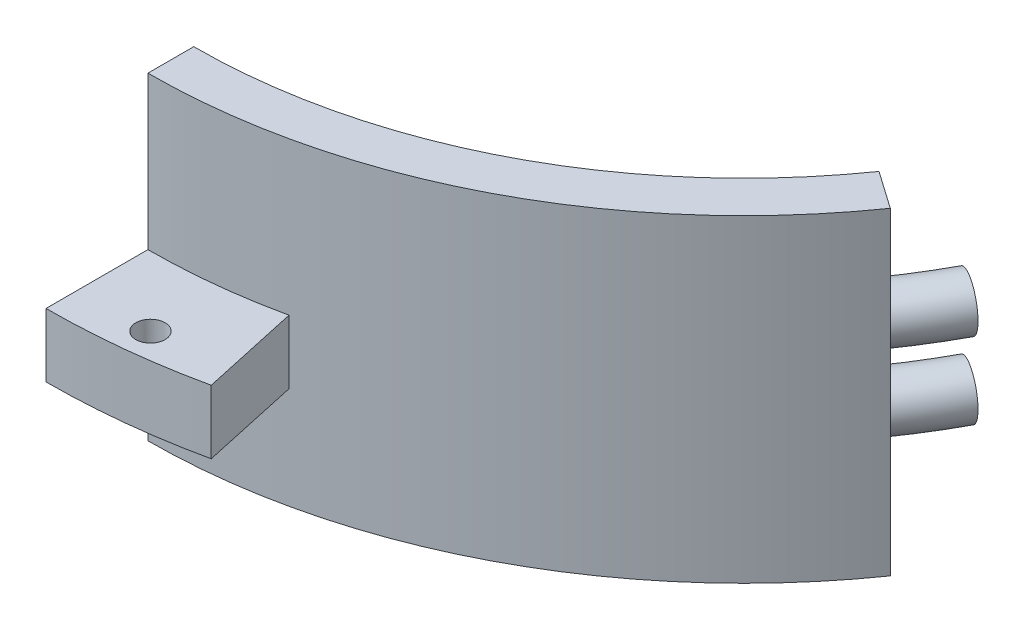
SolidWorks part; units mm, degrees
ref_plane "Front Plane" through (0, 0, 0) normal (0, 0, 1) x (1, 0, 0)
ref_plane "Top Plane" through (0, 0, 0) normal (0, 1, 0) x (1, 0, 0)
ref_plane "Right Plane" through (0, 0, 0) normal (1, 0, 0) x (0, 0, -1)
sketch "Sketch2" plane through (0, 0, 0) normal (0, 1, 0) x (1, 0, 0)
  line L0 (0, -46.8) -> (0, -43.2)
  line L1 (38.3363, -26.8434) -> (35.3874, -24.7785)
  line L2 (0, 0) -> (35.3874, -24.7785) construction
  circle A0 centre (0, 0) radius 46.8
  circle A1 centre (0, 0) radius 43.2
  dimension "D1" = 93.6
  dimension "D3" = 55
  dimension "D2" = 3.6
extrude "Boss-Extrude1" add sketch "Sketch2" along normal blind 25 contours A1 L0 A0 L1 region at (20.0007, 0, 38.421)
sketch "Sketch3" plane through (0, 25, 0) normal (0, 1, 0) x (1, 0, 0)
  line L0 (0, -43.2) -> (0, -40)
  line L1 (35.3874, -24.7785) -> (32.7661, -22.9431)
  line L2 (38.3363, -26.8434) -> (35.3874, -24.7785) construction
  circle A0 centre (0, 0) radius 40
  circle A2 centre (0, 0) radius 44.8
  arc M6 (35.3874, -24.7785) -> (0, -43.2) centre (0, 0) cw
  dimension "D1" = 80
  dimension "D2" = 89.6
extrude "Boss-Extrude2" add sketch "Sketch3" against normal blind 13 from offset 6 contours A0 L0 L1 M6 region at (18.4888, 25, 35.5166) offset against normal yes
sketch "Sketch4" plane through (0, 25, 0) normal (0, 1, 0) x (1, 0, 0)
  line L0 (0, -46.8) -> (0, -54.8)
  line L1 (10, -45.7191) -> (11.7094, -53.5344)
  line L2 (0, 0) -> (10, -45.7191) construction
  circle A0 centre (0, 0) radius 54.8
  arc A2 (0, -46.8) -> (38.3363, -26.8434) centre (0, 0) ccw construction
  circle A3 centre (0, 0) radius 46.8
  arc M7 (0, -46.8) -> (38.3363, -26.8434) centre (0, 0) ccw
  dimension "D1" = 8
  dimension "D2" = 10
extrude "Boss-Extrude3" add sketch "Sketch4" against normal blind 5 from offset 12 contours L0 A0 L1 M7 region at (5.4597, 25, 50.5125) offset against normal yes
sketch "Sketch5" plane through (0, 13, 0) normal (0, 1, 0) x (1, 0, 0)
  line L0 (5.0291, -46.529) -> (5.8888, -54.4827) construction
  circle A0 centre (5.647, -52.2457) radius 1.15
  arc A1 (0, -46.8) -> (10, -45.7191) centre (0, 0) ccw construction
  arc A2 (0, -54.8) -> (11.7094, -53.5344) centre (0, 0) ccw construction
  dimension "D1" = 2.3
  dimension "D2" = 2.25
extrude "M2 holes" cut sketch "Sketch5" against normal up to next
sketch "Sketch6" plane through (0, 19, 0) normal (0, 1, 0) x (1, 0, 0)
  line L0 (0, -40) -> (0, -43)
  line L1 (0, -43.2) -> (0, -40) construction
  line L2 (0, -43) -> (5, -39.6863)
  arc A0 (0, -40) -> (32.7661, -22.9431) centre (0, 0) ccw construction
  arc A1 (0, -40) -> (5, -39.6863) centre (0, 0) ccw
  dimension "D1" = 3
  dimension "D2" = 5
extrude "Cut-Extrude1" cut sketch "Sketch6" against normal up to next
sketch "Sketch7" plane through (0, 0, 0) normal (0.5736, 0, -0.8192) x (-0.8192, 0, -0.5736)
  line L1 (-40, 6) -> (-40, 19) construction
  line L2 (-24.7785, 19) -> (-43.2, 19) construction
  line L3 (-43.2, 6) -> (-40, 6) construction
  circle A0 centre (-43.4, 15.5) radius 2
  circle A1 centre (-43.4, 9.5) radius 2
  point P4 (0, 0)
  dimension "D1" = 4
  dimension "D2" = 3.4
  dimension "D3" = 3.5
  dimension "D4" = 3.5
sketch "Sketch9" plane through (0, 25, 0) normal (0, 1, 0) x (1, 0, 0)
  line L0 (0, 0) -> (35.3874, -24.7785) construction
  line L1 (0, 0) -> (38.0134, -20.5236) construction
  arc A0 (35.3874, -24.7785) -> (38.0134, -20.5236) centre (0, 0) ccw
  arc A1 (0, -43.2) -> (35.3874, -24.7785) centre (0, 0) ccw construction
  point P1 (38.0134, -20.5236)
  dimension "D1" = 5
sweep "Sweep1" add profiles "Sketch7" path "Sketch9"
